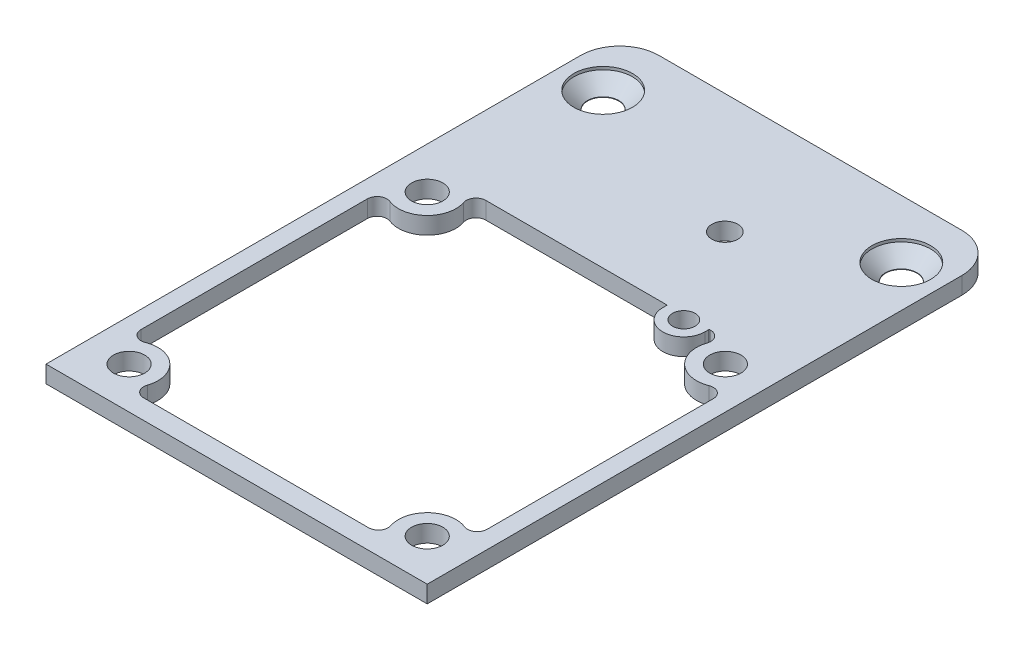
SolidWorks part; units mm, degrees
ref_plane "Front Plane" through (0, 0, 0) normal (0, 0, 1) x (1, 0, 0)
ref_plane "Top Plane" through (0, 0, 0) normal (0, 1, 0) x (1, 0, 0)
ref_plane "Right Plane" through (0, 0, 0) normal (1, 0, 0) x (0, 0, -1)
sketch "Sketch1" plane through (0, 0, 0) normal (0, 1, 0) x (1, 0, 0)
  line L0 (-15.5, 39.2) -> (15.5, 39.2)
  line L1 (-18.2, 15) -> (-18.2, -15) construction
  line L2 (17.7, -17.4996) -> (-17.7, -17.4996)
  line L3 (17.7, -17.4996) -> (17.7, 17.4996)
  line L4 (17.7, 17.4996) -> (-17.7, 17.4996)
  line L5 (-17.7, -17.4996) -> (-17.7, 17.4996)
  line L6 (17.7, -17.4996) -> (-17.7, 17.4996) construction
  line L7 (-19.5, 35.2) -> (-19.5, -19.5)
  line L8 (-19.5, -19.5) -> (19.5, -19.5)
  line L9 (19.5, -19.5) -> (19.5, 35.2)
  line L10 (17.7, 17.4996) -> (-17.7, -17.4996) construction
  line L11 (-15.25, 15.25) -> (-15.25, 17.9996) construction
  line L12 (11.35, 17.05) -> (11.35, 17.4996)
  line L13 (7.05, 17.05) -> (7.05, 17.4996)
  arc A0 (19.5, 35.2) -> (15.5, 39.2) centre (15.5, 35.2) ccw construction
  arc A1 (-15.5, 39.2) -> (-19.5, 35.2) centre (-15.5, 35.2) ccw construction
  arc A2 (19.5, 35.2) -> (15.5, 39.2) centre (15.5, 35.2) ccw
  arc A3 (-15.5, 39.2) -> (-19.5, 35.2) centre (-15.5, 35.2) ccw
  circle A4 centre (-15.25, -15.25) radius 1.6 construction
  circle A5 centre (15.25, -15.25) radius 1.6 construction
  circle A6 centre (-15.25, 15.25) radius 1.6 construction
  circle A7 centre (15.25, 15.25) radius 1.6 construction
  circle A8 centre (-15.25, 33.25) radius 1.6 construction
  circle A9 centre (15.25, 33.25) radius 1.6 construction
  circle A10 centre (-15.25, -15.25) radius 1.6
  circle A11 centre (15.25, -15.25) radius 1.6
  circle A12 centre (-15.25, 15.25) radius 1.6
  circle A13 centre (15.25, 15.25) radius 1.6
  circle A14 centre (-15.25, 33.25) radius 1.6
  circle A15 centre (15.25, 33.25) radius 1.6
  arc A16 (-15.2, 18) -> (-18.2, 15) centre (-15.2, 15) ccw construction
  circle A17 centre (-15.25, 15.25) radius 2.95
  circle A18 centre (15.25, 15.25) radius 2.95
  circle A19 centre (-15.25, -15.25) radius 2.95
  circle A20 centre (15.25, -15.25) radius 2.95
  circle A21 centre (3.5, 26.95) radius 1.33 construction
  circle A22 centre (9.2, 17.05) radius 2.15
  circle A23 centre (9.2, 17.05) radius 1.15
  circle A24 centre (9.2, 17.05) radius 0.9 construction
  circle A25 centre (3.5, 26.95) radius 1.33
  point P29 (0, 0)
  dimension "D3" = 2.3
  dimension "D4" = 1
  dimension "D1" = 0.5
  dimension "D2" = 0.5
extrude "Base shape" add sketch "Sketch1" along normal blind 1.75 contours L0 A3 L7 L8 L9 A2 A20 L3 L2 A19 L5 A17 L4 A18 A15 A14 | A17 L4 L5 | L4 A17 L5 A12 | L5 A17 | L4 A17 | L3 A18 L4 A13 | L3 A18 | L4 A18 | L2 A19 L5 A10 | L2 A19 | L5 A19 | A19 L5 L2 | L2 A20 L3 A11 | L3 A20 | L2 A20 | A20 L2 L3 | A18 L3 L4 | A23 L4 A22 | A23 L4 A22 | A22 L4 L13 | A22 L12 L4 region at (-0.0683, 0, -21.4041) region at (17.5279, 0, 17.307) region at (15.25, 0, 17.7828) region at (15.25, 0, 17.4246) region at (17.9015, 0, 15.25) region at (-15.25, 0, 17.7828) region at (-15.25, 0, 17.4246) region at (13.3348, 0, -13.1057) region at (17.9015, 0, -15.25) region at (-17.5279, 0, 17.307) region at (17.5279, 0, -17.307) region at (15.25, 0, -17.7828) region at (-17.9015, 0, 15.25) region at (11.3358, 0, -17.3874) region at (-17.9015, 0, -15.25) region at (-17.625, 0, -15.25) region at (11.2881, 0, -17.2708) region at (9.2, 0, -18.3154) region at (-17.5279, 0, -17.307) region at (7.0642, 0, -17.3874) region at (-15.25, 0, -17.7828)
fillet "Milling fillets" radius 1 8 edges at (-17.7, 0.875, 13.6068) (-13.3416, 0.875, 17.4996) (13.3416, 0.875, 17.4996) (17.7, 0.875, 13.6068) (17.7, 0.875, -13.6068) (13.3416, 0.875, -17.4996) (-13.3416, 0.875, -17.4996) (-17.7, 0.875, -13.6068)
sketch "Sketch3" plane through (0, 1.75, 0) normal (0, 1, 0) x (1, 0, 0)
  circle A0 centre (-15.25, 33.25) radius 3
  circle A1 centre (15.25, 33.25) radius 3
  dimension "D1" = 6
extrude "Screw head cut" cut sketch "Sketch3" against normal blind 0.3
chamfer "Screw head chamfer" distance 1.4 angle 45 2 edges at (15.25, 1.45, -31.65) (-15.25, 1.45, -31.65)
